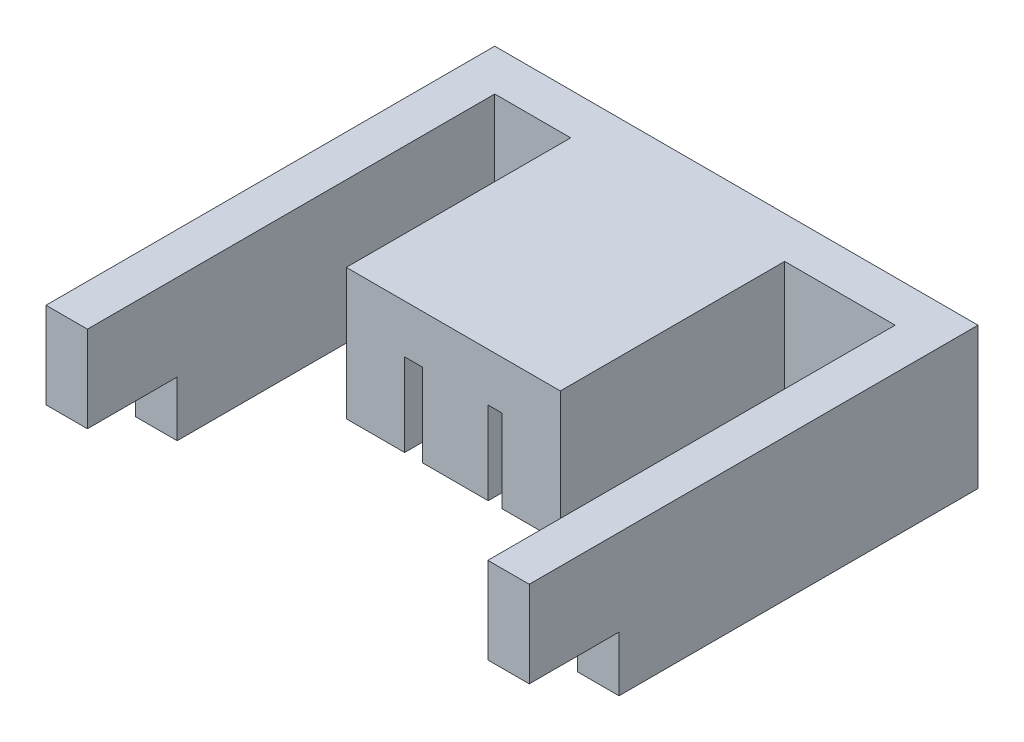
SolidWorks part; units mm, degrees
material "PBT General Purpose"
ref_plane "Front Plane" through (0, 0, 0) normal (0, 0, 1) x (1, 0, 0)
ref_plane "Top Plane" through (0, 0, 0) normal (0, 1, 0) x (1, 0, 0)
ref_plane "Right Plane" through (0, 0, 0) normal (1, 0, 0) x (0, 0, -1)
sketch "Sketch1" plane through (0, 0, 0) normal (0, 1, 0) x (1, 0, 0)
  line L0 (29, -32.5) -> (35, -32.5)
  line L1 (-35, 32.5) -> (35, 32.5)
  line L2 (-35, 32.5) -> (-35, -32.5)
  line L3 (-35, -32.5) -> (-29, -32.5)
  line L4 (35, 32.5) -> (35, -32.5)
  line L5 (-29, 26.5) -> (29, 26.5)
  line L6 (-29, 26.5) -> (-29, -32.5)
  line L8 (29, 26.5) -> (29, -32.5)
  point P8 (0, 26.5)
  point P10 (-35, 0)
  dimension "D1" = 70
  dimension "D2" = 65
  dimension "D3" = 6
  dimension "D4" = 6
  dimension "D5" = 6
extrude "Boss-Extrude1" add sketch "Sketch1" along normal blind 20.5
sketch "Sketch2" plane through (0, 0, 0) normal (0, -1, 0) x (1, 0, 0)
  line L0 (35, 32.5) -> (35, -32.5) construction
  line L1 (29, 32.5) -> (35, 32.5)
  line L2 (29, 32.5) -> (29, 19.5)
  line L3 (29, 19.5) -> (35, 19.5)
  line L4 (35, 32.5) -> (35, 19.5)
  line L5 (0, -1000) -> (0, 49000) construction
  line L6 (-29, -26.5) -> (29, -26.5) construction
  line L7 (-12.5, -26.5) -> (12.5, -26.5)
  line L8 (-12.5, -26.5) -> (-12.5, -32.5)
  line L9 (-12.5, -32.5) -> (12.5, -32.5)
  line L10 (12.5, -26.5) -> (12.5, -32.5)
  line L11 (35, -32.5) -> (-35, -32.5) construction
  line L12 (-29, 19.5) -> (-35, 19.5)
  line L13 (-35, 32.5) -> (-35, 19.5)
  line L14 (-29, 32.5) -> (-35, 32.5)
  line L15 (-29, 32.5) -> (-29, 19.5)
  point P18 (0, -26.5)
  point P19 (0, -26.5)
  dimension "D1" = 13
  dimension "D2" = 25
extrude "Cut-Extrude1" cut sketch "Sketch2" against normal blind 8
sketch "Sketch3" plane through (0, 20.5, 0) normal (0, 1, 0) x (1, 0, 0)
  line L0 (-29, -32.5) -> (-29, 26.5) construction
  line L1 (-14, 21) -> (9, 21)
  line L2 (-14, 21) -> (-14, -2)
  line L3 (-14, -2) -> (9, -2)
  line L4 (9, 21) -> (9, -2)
  line L5 (-29, 26.5) -> (29, 26.5) construction
  dimension "D1" = 23
  dimension "D2" = 23
  dimension "D3" = 15
  dimension "D4" = 5.5
extrude "Boss-Extrude2" add sketch "Sketch3" against normal offset from surface (7 mm away) 13.5 separate body up to face at (-25.5, 0, -13.1667)
sketch "Sketch4" plane through (0, 20.5, 0) normal (0, 1, 0) x (1, 0, 0)
  line L0 (-18, 26.5) -> (-18, -6)
  line L1 (-29, 26.5) -> (29, 26.5) construction
  line L2 (-18, -6) -> (13, -6)
  line L3 (13, -6) -> (13, 26.5)
  line L4 (-14, 21) -> (-14, -2)
  line L5 (-14, -2) -> (9, -2)
  line L6 (9, -2) -> (9, 21)
  line L7 (9, 21) -> (-14, 21)
  line L8 (-14, 21) -> (-14, -2)
  line L9 (-14, -2) -> (9, -2)
  line L10 (9, -2) -> (9, 21)
  line L11 (9, 21) -> (-14, 21)
  line L12 (13, 26.5) -> (-18, 26.5)
  line M12 (-29, 26.5) -> (29, 26.5)
  dimension "D2" = 4
  dimension "D3" = 4
  dimension "D4" = 4
  dimension "D1" = 0
extrude "Boss-Extrude4" add sketch "Sketch4" against normal offset from surface (19 mm away) 12 contours L2 L3 L0 L11 L10 L9 L8 M12 region at (-2.5, 20.5, -26.0509) up to face at (-2.5, 13.5, -9.5) offset beyond the face yes
sketch "Sketch5" plane through (0, 1.5, 0) normal (0, -1, 0) x (1, 0, 0)
  line L0 (-14, -21) -> (9, -21) construction
  line L1 (-6.95, -21) -> (-9.55, -21)
  line L2 (-6.95, -21) -> (-6.95, -26.5)
  line L3 (-6.95, -26.5) -> (-9.55, -26.5)
  line L4 (-9.55, -21) -> (-9.55, -26.5)
  line L5 (12.5, -26.5) -> (-12.5, -26.5) construction
  line L6 (9, 2) -> (-14, 2) construction
  line L7 (-9.55, 2) -> (-6.95, 2)
  line L8 (-9.55, 2) -> (-9.55, 6)
  line L9 (-9.55, 6) -> (-6.95, 6)
  line L10 (-6.95, 2) -> (-6.95, 6)
  line L11 (13, 6) -> (-18, 6) construction
  line L12 (-18, 6) -> (-18, -26.5) construction
  line L13 (-18, 2) -> (-14, 2)
  line L14 (-18, 2) -> (-18, -13)
  line L15 (-18, -13) -> (-14, -13)
  line L16 (-14, 2) -> (-14, -13)
  line L17 (-14, 2) -> (-14, -21) construction
  line L18 (9, 2) -> (-14, 2) construction
  line L19 (2.55, 6) -> (4.55, 6)
  line L20 (2.55, 6) -> (2.55, 2)
  line L21 (2.55, 2) -> (4.55, 2)
  line L22 (4.55, 6) -> (4.55, 2)
  line L23 (-14, 2) -> (-14, -21) construction
  dimension "D1" = 2
  dimension "D2" = 9.5
  dimension "D3" = 15
  dimension "D4" = 2.6
  dimension "D5" = 4.45
extrude "Cut-Extrude2" cut sketch "Sketch5" against normal up to surface (12 mm away) up to face at (-2.5, 13.5, -9.5)
sketch "Sketch6" plane through (0, 0, 0) normal (0, -1, 0) x (1, 0, 0)
  line L1 (-35, 19.5) -> (-29, 19.5) construction
  line L2 (-29, -26.5) -> (-12.5, -26.5) construction
  circle A0 centre (-32, 14.5) radius 1.5
  circle A1 centre (-32, -21.5) radius 1.5
  point P6 (-32, 19.5)
  dimension "D1" = 3
  dimension "D3" = 3
  dimension "D2" = 5
  dimension "D4" = 5
extrude "Cut-Extrude3" cut sketch "Sketch6" against normal blind 10
mirror "Mirror1" about plane through (0, 0, 0) normal (1, 0, 0) of "Cut-Extrude3"
equation "\"body_height\"= 41mm"
equation "\"D1@Boss-Extrude1\"=\"body_height\" / 2"
equation "\"D1@Boss-Extrude2\"=12+1.5"
